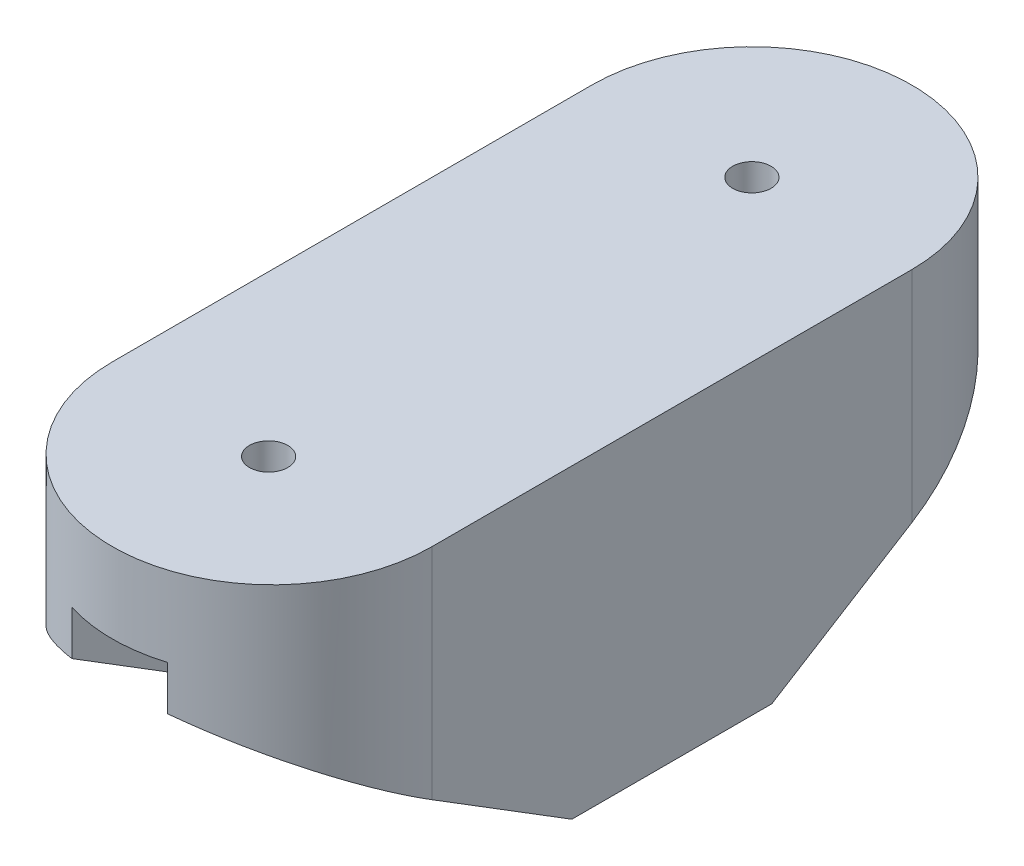
SolidWorks part; units mm, degrees
ref_plane "Front Plane" through (0, 0, 0) normal (0, 0, 1) x (1, 0, 0)
ref_plane "Top Plane" through (0, 0, 0) normal (0, 1, 0) x (1, 0, 0)
ref_plane "Right Plane" through (0, 0, 0) normal (1, 0, 0) x (0, 0, -1)
sketch "Sketch1" plane through (0, 0, 0) normal (0, 1, 0) x (1, 0, 0)
  line L0 (0, 0) -> (0, -38.1) construction
  line L1 (12.7, 0) -> (12.7, -38.1)
  line L2 (-12.7, 0) -> (-12.7, -38.1)
  line L3 (0, -35.5951) -> (-2.1693, -36.8476) construction
  line L4 (-2.1693, -36.8476) -> (-2.1693, -39.3524) construction
  line L5 (-2.1693, -39.3524) -> (0, -40.6049) construction
  line L6 (0, -40.6049) -> (2.1693, -39.3524) construction
  line L7 (2.1693, -39.3524) -> (2.1693, -36.8476) construction
  line L8 (2.1693, -36.8476) -> (0, -35.5951) construction
  line L9 (0, 3.0794) -> (-2.1693, 1.8269) construction
  line L10 (-2.1693, 1.8269) -> (-2.1693, -0.678) construction
  line L11 (-2.1693, -0.678) -> (0, -1.9304) construction
  line L12 (0, -1.9304) -> (2.1693, -0.678) construction
  line L13 (2.1693, -0.678) -> (2.1693, 1.8269) construction
  line L14 (2.1693, 1.8269) -> (0, 3.0794) construction
  arc A0 (12.7, 0) -> (-12.7, 0) centre (0, 0) ccw
  arc A1 (-12.7, -38.1) -> (12.7, -38.1) centre (0, -38.1) ccw
  circle A2 centre (0, -38.1) radius 2.1693 construction
  circle A3 centre (0, 0.5745) radius 2.1693 construction
  circle A4 centre (0, -38.1) radius 1.524 construction
  circle A5 centre (0, 0.5745) radius 1.524 construction
  point P3 (0, -19.05)
extrude "Boss-Extrude1" add sketch "Sketch1" against normal blind 6.35
sketch "Sketch2" plane through (0, 0, 0) normal (1, 0, 0) x (0, 0, -1)
  line L0 (-19.05, -6.35) -> (-19.05, -31.75) construction
  line L1 (12.7, -6.35) -> (-50.8, -6.35) construction
  line L2 (12.7, -6.35) -> (12.7, -12.7) construction
  line L3 (12.7, -12.7) -> (-11.1189, -37.0247) construction
  line L4 (-11.1189, -37.0247) -> (-26.9938, -37.0056) construction
  line L5 (-26.9938, -37.0056) -> (-50.8, -12.7) construction
  line L6 (-50.8, -12.7) -> (-50.8, -6.35) construction
  line L7 (-50.8, -6.35) -> (12.7, -6.35)
  line L8 (12.7, -6.35) -> (12.7, -9.525)
  line L9 (-19.05, -6.35) -> (-19.05, -9.525) construction
  line L10 (-11.1188, -24.3056) -> (-26.9938, -24.3056)
  line L11 (12.7, -9.525) -> (-11.1188, -24.3056)
  line L12 (-50.8, -6.35) -> (-50.8, -9.525)
  line L13 (-50.8, -9.525) -> (-26.9938, -24.3056)
  circle A0 centre (-19.05, -31.75) radius 9.525 construction
  circle A1 centre (-19.05, -19.05) radius 9.525 construction
extrude "Boss-Extrude3" add sketch "Sketch2" along normal through all and the other way through all
sketch "Sketch10" plane through (0, -6.35, 0) normal (0, 1, 0) x (1, 0, 0)
  line L0 (0, 0) -> (0, -38.1) construction
  line L1 (12.7, 0) -> (12.7, -38.1)
  line L2 (-12.7, 0) -> (-12.7, -38.1)
  line L3 (-12.7, 0) -> (12.7, -38.1) construction
  line L4 (12.7, -38.1) -> (0, -19.05) construction
  line L6 (-12.7, -50.8) -> (12.7, -50.8)
  line L7 (-12.7, -50.8) -> (-12.7, 12.7)
  line L8 (-12.7, 12.7) -> (12.7, 12.7)
  line L9 (12.7, -50.8) -> (12.7, 12.7)
  line L10 (-12.7, -50.8) -> (12.7, 12.7) construction
  line L11 (-12.7, 12.7) -> (12.7, -50.8) construction
  arc A0 (12.7, 0) -> (-12.7, 0) centre (0, 0) ccw
  arc A1 (-12.7, -38.1) -> (12.7, -38.1) centre (0, -38.1) ccw
  arc A2 (-12.7, -38.1) -> (12.7, -38.1) centre (0, -38.1) ccw construction
  arc A3 (0, -50.8) -> (12.7, -38.1) centre (0, -38.1) ccw construction
  point P2 (0, -19.05)
  arc M1 (0, 12.7) -> (12.7, 0) centre (0, 0) cw
  line M2 (12.7, 0) -> (12.7, 12.7)
  line M17 (12.7, 12.7) -> (0, 12.7)
sketch "Sketch11" plane through (0, 0, 0) normal (0, 0, 1) x (1, 0, 0)
  line L0 (0, 0) -> (0, -6.35) construction
  line L2 (12.7, -6.35) -> (0, -6.35) construction
  line L3 (-3.7847, -35.5514) -> (3.81, -35.5514)
  line L4 (-3.7847, -35.5514) -> (-3.7847, -6.35)
  line L5 (-3.7847, -6.35) -> (3.81, -6.35)
  line L6 (3.81, -35.5514) -> (3.81, -6.35)
  line L7 (-3.7847, -35.5514) -> (3.81, -6.35) construction
  line L8 (-3.7847, -6.35) -> (3.81, -35.5514) construction
  point P2 (0.0126, -20.9507)
extrude "Cut-Extrude13" cut sketch "Sketch11" against normal through all and the other way through all
extrude "Cut-Extrude19" cut sketch "Sketch10" against normal through all contours A0 L8 L7 | M17 M1 M2 | A1 L7 L6 | A1 L6 L9 region at (9.8632, -6.35, -9.8632) region at (9.8632, -6.35, 47.9632) region at (-9.8632, -6.35, -9.8632) region at (-9.8632, -6.35, 47.9632)
sketch "Sketch16" plane through (0, -6.35, 0) normal (0, -1, 0) x (1, 0, 0)
  line L0 (0.0126, 2.2208) -> (-2.1567, 0.9684)
  line L1 (-2.1567, 0.9684) -> (-2.1567, -1.5365)
  line L2 (-2.1567, -1.5365) -> (0.0126, -2.789)
  line L3 (0.0126, -2.789) -> (2.1819, -1.5365)
  line L4 (2.1819, -1.5365) -> (2.1819, 0.9684)
  line L5 (2.1819, 0.9684) -> (0.0126, 2.2208)
  line L6 (0.0126, 40.8953) -> (-2.1567, 39.6429)
  line L7 (-2.1567, 39.6429) -> (-2.1567, 37.138)
  line L8 (-2.1567, 37.138) -> (0.0126, 35.8855)
  line L9 (0.0126, 35.8855) -> (2.1819, 37.138)
  line L10 (2.1819, 37.138) -> (2.1819, 39.6429)
  line L11 (2.1819, 39.6429) -> (0.0126, 40.8953)
  line L12 (0.0126, 38.3904) -> (0.0126, -0.2841) construction
  line L13 (-3.7847, 50.223) -> (-3.7847, -12.123) construction
  line L14 (-3.7847, 19.05) -> (3.81, 19.0563) construction
  line L15 (3.81, 26.9938) -> (3.81, 11.1188) construction
  circle A0 centre (0.0126, -0.2841) radius 2.1693 construction
  circle A1 centre (0.0126, 38.3904) radius 2.1693 construction
  circle A2 centre (0.0126, -0.2841) radius 1.524 construction
  circle A3 centre (0.0126, 38.3904) radius 1.524 construction
extrude "Cut-Extrude20" cut sketch "Sketch16" against normal blind 1.778
sketch "Sketch17" plane through (0, -4.572, 0) normal (0, -1, 0) x (1, 0, 0)
  line L0 (-2.1567, 39.6429) -> (2.1819, 37.138) construction
  circle A0 centre (0.0126, 38.3904) radius 1.524
  circle A1 centre (0, 0) radius 1.524
extrude "Cut-Extrude21" cut sketch "Sketch17" against normal through all
